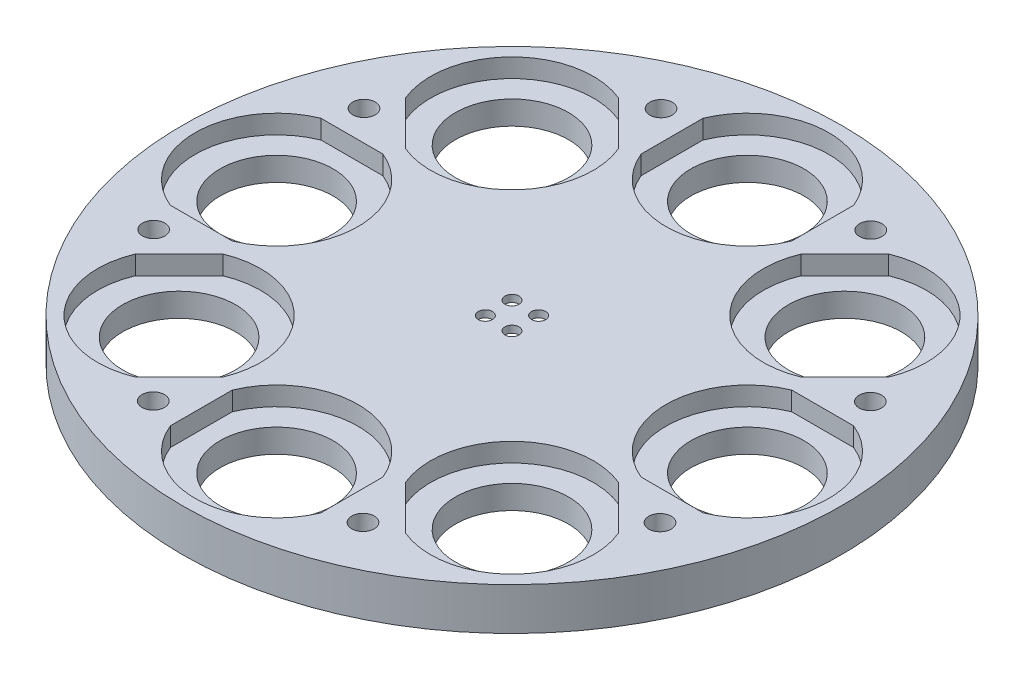
SolidWorks part; units mm, degrees
ref_plane "Front Plane" through (0, 0, 0) normal (0, 0, 1) x (1, 0, 0)
ref_plane "Top Plane" through (0, 0, 0) normal (0, 1, 0) x (1, 0, 0)
ref_plane "Right Plane" through (0, 0, 0) normal (1, 0, 0) x (0, 0, -1)
sketch "Sketch1" plane through (0, 0, 0) normal (0, 1, 0) x (1, 0, 0)
  line L0 (70, 0) -> (50, 0) construction
  circle A0 centre (0, 0) radius 70
  circle A1 centre (50, 0) radius 12
  circle A2 centre (35.3553, -35.3553) radius 12
  circle A3 centre (0, -50) radius 12
  circle A4 centre (-35.3553, -35.3553) radius 12
  circle A5 centre (-50, 0) radius 12
  circle A6 centre (-35.3553, 35.3553) radius 12
  circle A7 centre (0, 50) radius 12
  circle A8 centre (35.3553, 35.3553) radius 12
  point P23 (0, 0)
  dimension "D1" = 140
  dimension "D3" = 24
  dimension "D2" = 20
  dimension "D4" = 8
extrude "Boss-Extrude1" add sketch "Sketch1" along normal blind 25
sketch "Sketch2" plane through (0, 25, 0) normal (0, 1, 0) x (1, 0, 0)
  line L0 (50, 0) -> (50, 16) construction
  line L1 (50, 16) -> (43.4205, 16)
  line L2 (50, 16) -> (56.5795, 16)
  line L3 (32.7, 0) -> (67.3, 0) construction
  line L4 (50, -16) -> (56.5795, -16)
  line L5 (50, -16) -> (43.4205, -16)
  line L6 (46.669, -24.0416) -> (42.0166, -19.3892)
  line L7 (24.0416, -46.669) -> (19.3892, -42.0166)
  line L8 (24.0416, -46.669) -> (28.694, -51.3215)
  line L9 (46.669, -24.0416) -> (51.3215, -28.694)
  line L10 (16, -50) -> (16, -43.4205)
  line L11 (-16, -50) -> (-16, -43.4205)
  line L12 (-16, -50) -> (-16, -56.5795)
  line L13 (16, -50) -> (16, -56.5795)
  line L14 (-24.0416, -46.669) -> (-19.3892, -42.0166)
  line L15 (-46.669, -24.0416) -> (-42.0166, -19.3892)
  line L16 (-46.669, -24.0416) -> (-51.3215, -28.694)
  line L17 (-24.0416, -46.669) -> (-28.694, -51.3215)
  line L18 (-50, -16) -> (-43.4205, -16)
  line L19 (-50, 16) -> (-43.4205, 16)
  line L20 (-50, 16) -> (-56.5795, 16)
  line L21 (-50, -16) -> (-56.5795, -16)
  line L22 (-46.669, 24.0416) -> (-42.0166, 19.3892)
  line L23 (-24.0416, 46.669) -> (-19.3892, 42.0166)
  line L24 (-24.0416, 46.669) -> (-28.694, 51.3215)
  line L25 (-46.669, 24.0416) -> (-51.3215, 28.694)
  line L26 (-16, 50) -> (-16, 43.4205)
  line L27 (16, 50) -> (16, 43.4205)
  line L28 (16, 50) -> (16, 56.5795)
  line L29 (-16, 50) -> (-16, 56.5795)
  line L30 (24.0416, 46.669) -> (19.3892, 42.0166)
  line L31 (46.669, 24.0416) -> (42.0166, 19.3892)
  line L32 (46.669, 24.0416) -> (51.3215, 28.694)
  line L33 (24.0416, 46.669) -> (28.694, 51.3215)
  arc A0 (43.4205, 16) -> (43.4205, -16) centre (50, 0) ccw
  arc A1 (56.5795, -16) -> (56.5795, 16) centre (50, 0) ccw
  arc A2 (42.0166, -19.3892) -> (19.3892, -42.0166) centre (35.3553, -35.3553) ccw
  arc A3 (28.694, -51.3215) -> (51.3215, -28.694) centre (35.3553, -35.3553) ccw
  arc A4 (16, -43.4205) -> (-16, -43.4205) centre (0, -50) ccw
  arc A5 (-16, -56.5795) -> (16, -56.5795) centre (0, -50) ccw
  arc A6 (-19.3892, -42.0166) -> (-42.0166, -19.3892) centre (-35.3553, -35.3553) ccw
  arc A7 (-51.3215, -28.694) -> (-28.694, -51.3215) centre (-35.3553, -35.3553) ccw
  arc A8 (-43.4205, -16) -> (-43.4205, 16) centre (-50, 0) ccw
  arc A9 (-56.5795, 16) -> (-56.5795, -16) centre (-50, 0) ccw
  arc A10 (-42.0166, 19.3892) -> (-19.3892, 42.0166) centre (-35.3553, 35.3553) ccw
  arc A11 (-28.694, 51.3215) -> (-51.3215, 28.694) centre (-35.3553, 35.3553) ccw
  arc A12 (-16, 43.4205) -> (16, 43.4205) centre (0, 50) ccw
  arc A13 (16, 56.5795) -> (-16, 56.5795) centre (0, 50) ccw
  arc A14 (19.3892, 42.0166) -> (42.0166, 19.3892) centre (35.3553, 35.3553) ccw
  arc A15 (51.3215, 28.694) -> (28.694, 51.3215) centre (35.3553, 35.3553) ccw
  point P61 (0, 0)
  dimension "D1" = 34.6
  dimension "D2" = 16
  dimension "D3" = 8
extrude "Cut-Extrude1" cut sketch "Sketch2" against normal blind 10
ref_plane "Plane1" through (0, 10, 0) normal (0, 1, 0) x (1, 0, 0)
split "Split1" trim tools "Plane1" bodies to split 102 resulting bodies 103 104
delete or keep bodies "Body-Delete/Keep 1" type delete bodies bodies 104
sketch "Sketch3" plane through (0, 10, 0) normal (0, -1, 0) x (1, 0, 0)
  circle A0 centre (0, 0) radius 20
  dimension "D1" = 40
extrude "Cut-Extrude2" cut sketch "Sketch3" against normal blind 7.5
sketch "Sketch4" plane through (0, 25, 0) normal (0, 1, 0) x (1, 0, 0)
  circle A0 centre (0, 0) radius 70
extrude "Cut-Extrude3" cut sketch "Sketch4" against normal blind 6
sketch "Sketch5" plane through (0, 17.5, 0) normal (0, -1, 0) x (1, 0, 0)
  circle A0 centre (2.8254, 2.8314) radius 1.5
  circle A1 centre (2.8314, -2.8254) radius 1.5
  circle A2 centre (-2.8254, -2.8314) radius 1.5
  circle A3 centre (-2.8314, 2.8254) radius 1.5
  dimension "D1" = 3
extrude "Cut-Extrude4" cut sketch "Sketch5" against normal through all
sketch "Sketch7" plane through (0, 19, 0) normal (0, 1, 0) x (1, 0, 0)
  circle A0 centre (-22.2295, 53.882) radius 2.3813
  circle A1 centre (22.3817, 53.819) radius 2.3813
  circle A2 centre (53.882, 22.2295) radius 2.3813
  circle A3 centre (53.819, -22.3817) radius 2.3813
  circle A4 centre (22.2295, -53.882) radius 2.3813
  circle A5 centre (-22.3817, -53.819) radius 2.3813
  circle A6 centre (-53.882, -22.2295) radius 2.3812
  circle A7 centre (-53.819, 22.3817) radius 2.3812
  point P20 (0, 0)
  dimension "D1" = 4.7625
  dimension "D2" = 8
extrude "Cut-Extrude5" cut sketch "Sketch7" against normal through all
